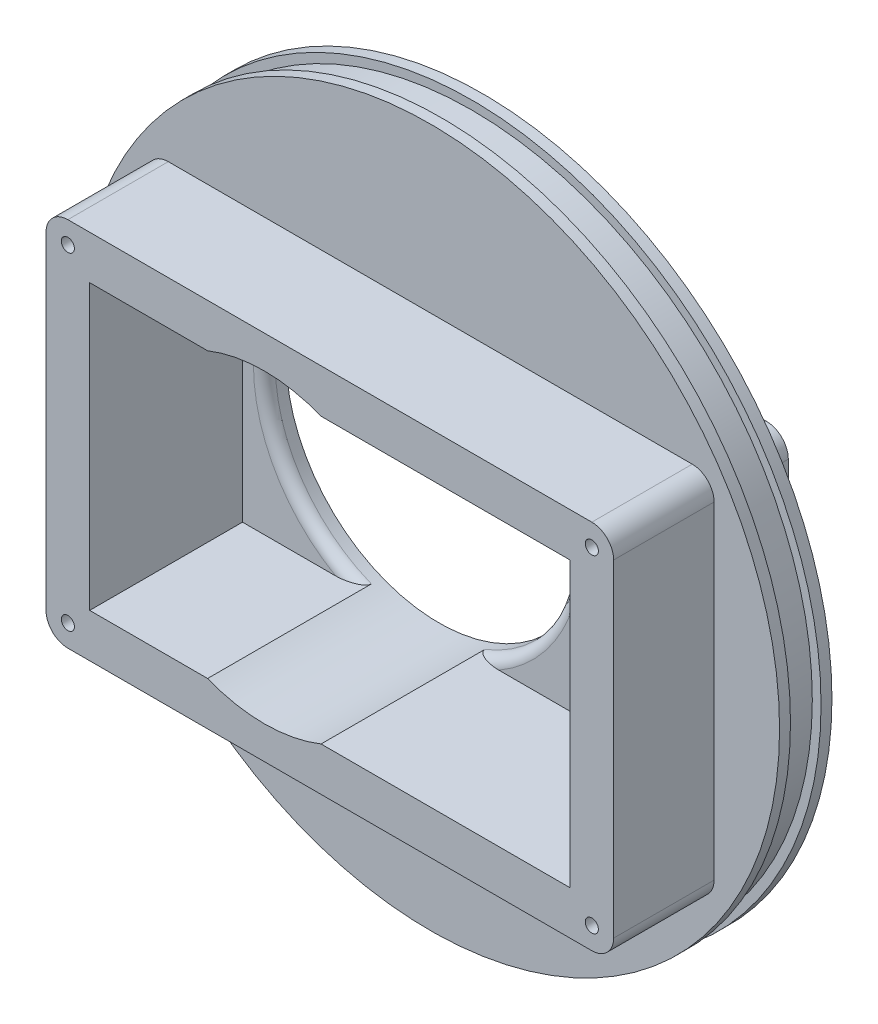
SolidWorks part; units mm, degrees
material "ABS"
ref_plane "Front" through (0, 0, 0) normal (0, 0, 1) x (1, 0, 0)
ref_plane "Top" through (0, 0, 0) normal (0, 1, 0) x (1, 0, 0)
ref_plane "Right" through (0, 0, 0) normal (1, 0, 0) x (0, 0, -1)
sketch "Sketch1" plane through (0, 0, 0) normal (0, 0, 1) x (1, 0, 0)
  line L1 (-55, -32.5) -> (55, -32.5)
  line L2 (-55, -32.5) -> (-55, 32.5)
  line L3 (-55, 32.5) -> (55, 32.5)
  line L4 (55, -32.5) -> (55, 32.5)
  line L5 (-55, -32.5) -> (55, 32.5) construction
  line L6 (-55, 32.5) -> (55, -32.5) construction
  line L7 (-65, -42.5) -> (65, -42.5)
  line L8 (-65, -42.5) -> (-65, 42.5)
  line L9 (-65, 42.5) -> (65, 42.5)
  line L10 (65, -42.5) -> (65, 42.5)
  line L11 (-65, -42.5) -> (65, 42.5) construction
  line L12 (-65, 42.5) -> (65, -42.5) construction
  point P0 (0, 0)
  point P6 (0, 0)
  dimension "D1" = 110
  dimension "D2" = 65
  dimension "D3" = 130
  dimension "D4" = 85
extrude "Boss-Extrude1" add sketch "Sketch1" along normal blind 35
sketch "Sketch2" plane through (0, 0, 0) normal (0, 0, 1) x (1, 0, 0)
  line L0 (-15, 0) -> (0, 0) construction
  line L1 (65, -42.5) -> (-65, -42.5)
  line L2 (65, -42.5) -> (65, 42.5)
  line L3 (65, 42.5) -> (-65, 42.5)
  line L4 (-65, -42.5) -> (-65, 42.5)
  line L5 (65, -42.5) -> (-65, 42.5) construction
  line L6 (65, 42.5) -> (-65, -42.5) construction
  line L8 (30, 42.5) -> (30, -42.5) construction
  line L10 (55, 32.5) -> (30, 32.5)
  line L11 (55, 32.5) -> (-55, 32.5) construction
  line L12 (30, 32.5) -> (30, -32.5)
  line L13 (30, -32.5) -> (55, -32.5)
  line L14 (55, -32.5) -> (55, 32.5)
  circle A0 centre (-15, 0) radius 35
  point P0 (0, 0)
  dimension "D2" = 70
  dimension "D1" = 15
  dimension "D3" = 35
extrude "Boss-Extrude2" add sketch "Sketch2" against normal blind 5
extrude "Cut-Extrude1" cut sketch "Sketch2<2>" along normal blind 45 contours A0
sketch "Sketch2<2>" plane through (0, 0, 0) normal (0, 0, 1) x (1, 0, 0) same geometry as "Sketch2"
sketch "Sketch3" plane through (0, 0, 35) normal (0, 0, 1) x (1, 0, 0)
  line L1 (-60, -37.5) -> (60, -37.5) construction
  line L2 (-60, -37.5) -> (-60, 37.5) construction
  line L3 (-60, 37.5) -> (60, 37.5) construction
  line L4 (60, -37.5) -> (60, 37.5) construction
  line L5 (-60, -37.5) -> (60, 37.5) construction
  line L6 (-60, 37.5) -> (60, -37.5) construction
  circle A0 centre (-60, 37.5) radius 1.5
  circle A1 centre (60, 37.5) radius 1.5
  circle A2 centre (-60, -37.5) radius 1.5
  circle A3 centre (60, -37.5) radius 1.5
  point P0 (0, 0)
  dimension "D3" = 3
  dimension "D4" = 3
  dimension "D5" = 3
  dimension "D6" = 3
  dimension "D1" = 120
  dimension "D2" = 75
extrude "Cut-Extrude2" cut sketch "Sketch3" against normal blind 15
fillet "Fillet1" radius 5 4 edges at (65, -42.5, 15) (-65, -42.5, 15) (65, 42.5, 15) (-65, 42.5, 15)
fillet "Fillet2" radius 2.5 3 edges at (30, 0, 0) (20, 0, 0) (-50, 0, 0)
sketch "Sketch4" plane through (0, 0, 0) normal (0, 0, 1) x (1, 0, 0)
  line L0 (60, 42.5) -> (-60, 42.5)
  line L1 (-60, 42.5) -> (-65, 37.5)
  line L2 (-65, 37.5) -> (-65, -37.5)
  line L3 (-65, -37.5) -> (-60, -42.5)
  line L4 (-60, -42.5) -> (60, -42.5)
  line L5 (60, -42.5) -> (65, -37.5)
  line L6 (65, -37.5) -> (65, 37.5)
  line L7 (65, 37.5) -> (60, 42.5)
  circle A0 centre (0, 0) radius 80
  dimension "D1" = 160
extrude "Boss-Extrude3" add sketch "Sketch4" along normal blind 12
sketch "Sketch5" plane through (0, 0, 0) normal (1, 0, 0) x (0, 0, -1)
  line L0 (0, 0) -> (77.0929, 0) construction
  line L1 (-9.5, 80) -> (-2.5, 80)
  line L2 (-9.5, 80) -> (-9.5, 78)
  line L3 (-9.5, 78) -> (-2.5, 78)
  line L4 (-2.5, 80) -> (-2.5, 78)
  dimension "D1" = 7
  dimension "D2" = 2.5
  dimension "D3" = 2
  dimension "D4" = 80
revolve "Cut-Revolve1" cut sketch "Sketch5" angle 360 about L0
